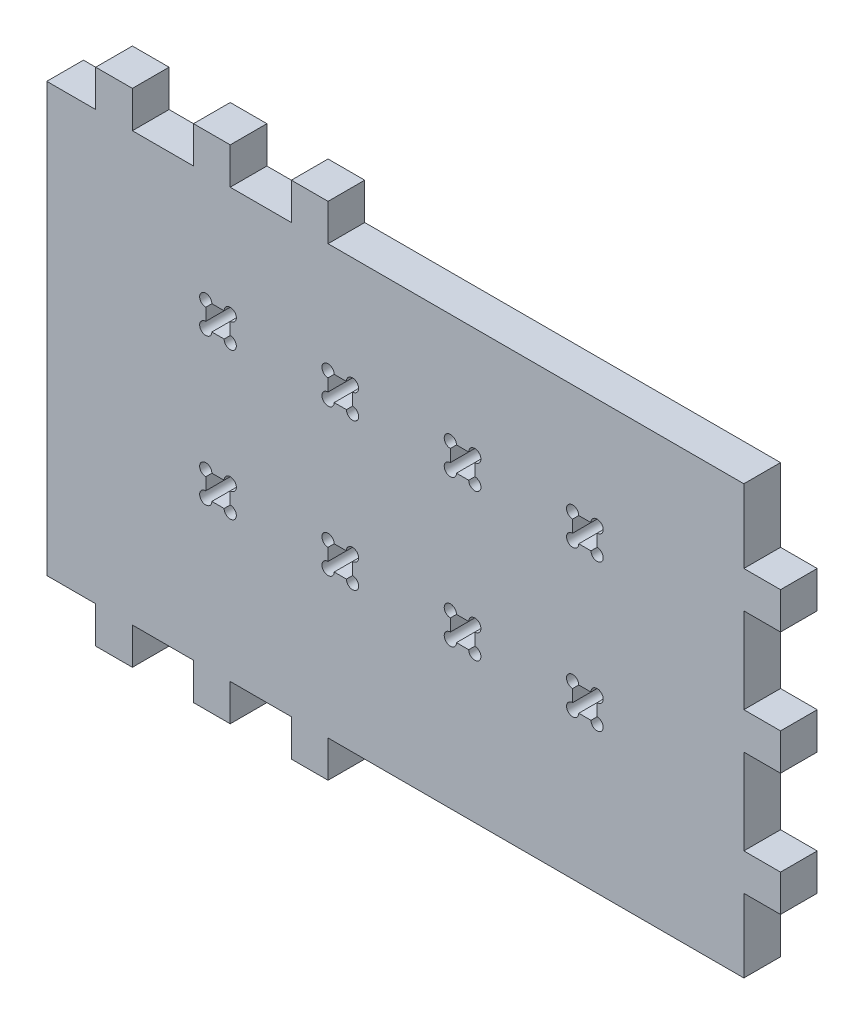
SolidWorks part; units mm, degrees
material "Balsa"
ref_plane "Front Plane" through (0, 0, 0) normal (0, 0, 1) x (1, 0, 0)
ref_plane "Top Plane" through (0, 0, 0) normal (0, 1, 0) x (1, 0, 0)
ref_plane "Right Plane" through (0, 0, 0) normal (1, 0, 0) x (0, 0, -1)
sketch "Sketch1" plane through (0, 0, 0) normal (0, 0, 1) x (1, 0, 0)
  line L1 (0, 0) -> (361.95, 0)
  line L2 (0, 0) -> (0, 222.25)
  line L3 (0, 222.25) -> (361.95, 222.25)
  line L4 (361.95, 0) -> (361.95, 222.25)
  dimension "D1" = 361.95
  dimension "D2" = 222.25
extrude "Boss-Extrude1" add sketch "Sketch1" against normal blind 19.05
sketch "Sketch2" plane through (0, 0, 0) normal (0, 0, 1) x (1, 0, 0)
  line L0 (0, 152.4) -> (361.95, 152.4)
  line L3 (0, 82.55) -> (361.95, 82.55)
  line L4 (0, 12.7) -> (361.95, 12.7) construction
  line L6 (0, 0) -> (361.95, 0) construction
  line L7 (0, 222.25) -> (0, 0) construction
  line L8 (361.95, 0) -> (361.95, 222.25) construction
  line L9 (0, 152.4) -> (-25.4, 152.4)
  line L10 (0, 82.55) -> (-25.4, 82.55)
  line L11 (0, 12.7) -> (-25.4, 12.7) construction
  line L12 (361.95, 12.7) -> (387.35, 12.7) construction
  line L13 (361.95, 82.55) -> (387.35, 82.55)
  line L14 (361.95, 152.4) -> (387.35, 152.4)
  dimension "D1" = 69.85
  dimension "D2" = 69.85
  dimension "D3" = 69.85
  dimension "5" = 0
  dimension "D4" = 25.4
  dimension "D5" = 12.7
sketch "Sketch3" plane through (0, 0, 0) normal (0, 0, 1) x (1, 0, 0)
  line L0 (44.45, 241.3) -> (76.2, 241.3) construction
  line L5 (95.25, 241.3) -> (127, 241.3) construction
  line L10 (361.95, 222.25) -> (0, 222.25) construction
  line L11 (25.4, 222.25) -> (44.45, 222.25)
  line L12 (25.4, 222.25) -> (25.4, 241.3)
  line L13 (25.4, 241.3) -> (44.45, 241.3)
  line L14 (44.45, 222.25) -> (44.45, 241.3)
  line L16 (0, 222.25) -> (0, 0) construction
  line L18 (76.2, 222.25) -> (95.25, 222.25)
  line L19 (76.2, 222.25) -> (76.2, 241.3)
  line L20 (76.2, 241.3) -> (95.25, 241.3)
  line L21 (95.25, 222.25) -> (95.25, 241.3)
  line L22 (146.05, 222.25) -> (127, 222.25)
  line L23 (146.05, 222.25) -> (146.05, 241.3)
  line L24 (146.05, 241.3) -> (127, 241.3)
  line L25 (127, 222.25) -> (127, 241.3)
  dimension "D1" = 19.05
  dimension "D2" = 25.4
  dimension "D3" = 127
extrude "Boss-Extrude4" add sketch "Sketch3" along direction (0, 0, -1) on the side against the normal up to surface (19.05 mm away) up to face at (180.975, 111.125, -19.05)
ref_plane "Plane1" through (0, 111.125, 0) normal (0, 1, 0) x (1, 0, 0)
mirror "Mirror1" about plane through (0, 111.125, 0) normal (0, 1, 0) of "Boss-Extrude4"
ref_plane "Plane2" through (0, 0, -9.525) normal (0, 0, 1) x (1, 0, 0)
sketch "Sketch5" plane through (0, 0, 0) normal (0, 0, 1) x (1, 0, 0)
  line L0 (361.95, 0) -> (361.95, 222.25) construction
  line L1 (361.95, 184.15) -> (381, 184.15)
  line L2 (361.95, 184.15) -> (361.95, 165.1)
  line L3 (361.95, 165.1) -> (381, 165.1)
  line L4 (381, 184.15) -> (381, 165.1)
  line L5 (361.95, 0) -> (361.95, 222.25) construction
  line L6 (361.95, 38.1) -> (381, 38.1)
  line L7 (361.95, 38.1) -> (361.95, 57.15)
  line L8 (361.95, 57.15) -> (381, 57.15)
  line L9 (381, 38.1) -> (381, 57.15)
  line L10 (361.95, 222.25) -> (361.95, 184.15) construction
  line L11 (361.95, 0) -> (361.95, 38.1) construction
  line L12 (361.95, 0) -> (361.95, 222.25) construction
  line L13 (361.95, 120.65) -> (381, 120.65)
  line L14 (361.95, 120.65) -> (361.95, 101.6)
  line L15 (361.95, 101.6) -> (381, 101.6)
  line L16 (381, 120.65) -> (381, 101.6)
  dimension "D1" = 19.05
  dimension "D2" = 38.1
  dimension "D3" = 44.45
  dimension "D4" = 38.1
extrude "Boss-Extrude5" add sketch "Sketch5" against normal up to surface (19.05 mm away) up to face at (99.3321, 111.125, -19.05)
sketch "Sketch6" plane through (0, 0, 0) normal (0, 0, 1) x (1, 0, 0)
  line L0 (0, 222.25) -> (0, 0) construction
  line L1 (85.725, 88.9) -> (92.075, 88.9)
  line L2 (82.55, 85.725) -> (82.55, 79.375)
  line L3 (85.725, 76.2) -> (92.075, 76.2)
  line L4 (95.25, 85.725) -> (95.25, 79.375)
  line L5 (0, 0) -> (25.4, 0) construction
  line L28 (149.225, 76.2) -> (155.575, 76.2)
  line L63 (158.75, 85.725) -> (158.75, 79.375)
  line L64 (149.225, 88.9) -> (155.575, 88.9)
  line L65 (44.45, -19.05) -> (25.4, -19.05) construction
  line L66 (146.05, 85.725) -> (146.05, 79.375)
  line L67 (212.725, 76.2) -> (219.075, 76.2)
  line L68 (222.25, 85.725) -> (222.25, 79.375)
  line L69 (212.725, 88.9) -> (219.075, 88.9)
  line L70 (209.55, 85.725) -> (209.55, 79.375)
  line L71 (276.225, 76.2) -> (282.575, 76.2)
  line L72 (285.75, 85.725) -> (285.75, 79.375)
  line L73 (276.225, 88.9) -> (282.575, 88.9)
  line L74 (273.05, 85.725) -> (273.05, 79.375)
  line L75 (149.225, 152.4) -> (155.575, 152.4)
  line L76 (158.75, 161.925) -> (158.75, 155.575)
  line L77 (149.225, 165.1) -> (155.575, 165.1)
  line L78 (146.05, 161.925) -> (146.05, 155.575)
  line L79 (212.725, 152.4) -> (219.075, 152.4)
  line L80 (222.25, 161.925) -> (222.25, 155.575)
  line L81 (212.725, 165.1) -> (219.075, 165.1)
  line L82 (209.55, 161.925) -> (209.55, 155.575)
  line L83 (276.225, 152.4) -> (282.575, 152.4)
  line L84 (285.75, 161.925) -> (285.75, 155.575)
  line L85 (276.225, 165.1) -> (282.575, 165.1)
  line L86 (273.05, 161.925) -> (273.05, 155.575)
  line L87 (85.725, 152.4) -> (92.075, 152.4)
  line L88 (95.25, 161.925) -> (95.25, 155.575)
  line L89 (85.725, 165.1) -> (92.075, 165.1)
  line L90 (82.55, 161.925) -> (82.55, 155.575)
  line L91 (82.55, 79.375) -> (146.05, 79.375) construction
  line L92 (82.55, 79.375) -> (82.55, 155.575) construction
  arc A20 (85.725, 88.9) -> (82.55, 85.725) centre (82.55, 88.9) ccw
  arc A21 (95.25, 85.725) -> (92.075, 88.9) centre (95.25, 88.9) ccw
  arc A22 (82.55, 79.375) -> (85.725, 76.2) centre (82.55, 76.2) ccw
  arc A23 (92.075, 76.2) -> (95.25, 79.375) centre (95.25, 76.2) ccw
  arc A24 (146.05, 79.375) -> (149.225, 76.2) centre (146.05, 76.2) ccw
  arc A25 (155.575, 76.2) -> (158.75, 79.375) centre (158.75, 76.2) ccw
  arc A26 (158.75, 85.725) -> (155.575, 88.9) centre (158.75, 88.9) ccw
  arc A27 (149.225, 88.9) -> (146.05, 85.725) centre (146.05, 88.9) ccw
  arc A28 (209.55, 79.375) -> (212.725, 76.2) centre (209.55, 76.2) ccw
  arc A29 (219.075, 76.2) -> (222.25, 79.375) centre (222.25, 76.2) ccw
  arc A30 (222.25, 85.725) -> (219.075, 88.9) centre (222.25, 88.9) ccw
  arc A31 (212.725, 88.9) -> (209.55, 85.725) centre (209.55, 88.9) ccw
  arc A32 (273.05, 79.375) -> (276.225, 76.2) centre (273.05, 76.2) ccw
  arc A33 (282.575, 76.2) -> (285.75, 79.375) centre (285.75, 76.2) ccw
  arc A34 (285.75, 85.725) -> (282.575, 88.9) centre (285.75, 88.9) ccw
  arc A35 (276.225, 88.9) -> (273.05, 85.725) centre (273.05, 88.9) ccw
  arc A36 (146.05, 155.575) -> (149.225, 152.4) centre (146.05, 152.4) ccw
  arc A37 (155.575, 152.4) -> (158.75, 155.575) centre (158.75, 152.4) ccw
  arc A38 (158.75, 161.925) -> (155.575, 165.1) centre (158.75, 165.1) ccw
  arc A39 (149.225, 165.1) -> (146.05, 161.925) centre (146.05, 165.1) ccw
  arc A40 (209.55, 155.575) -> (212.725, 152.4) centre (209.55, 152.4) ccw
  arc A41 (219.075, 152.4) -> (222.25, 155.575) centre (222.25, 152.4) ccw
  arc A42 (222.25, 161.925) -> (219.075, 165.1) centre (222.25, 165.1) ccw
  arc A43 (212.725, 165.1) -> (209.55, 161.925) centre (209.55, 165.1) ccw
  arc A44 (273.05, 155.575) -> (276.225, 152.4) centre (273.05, 152.4) ccw
  arc A45 (282.575, 152.4) -> (285.75, 155.575) centre (285.75, 152.4) ccw
  arc A46 (285.75, 161.925) -> (282.575, 165.1) centre (285.75, 165.1) ccw
  arc A47 (276.225, 165.1) -> (273.05, 161.925) centre (273.05, 165.1) ccw
  arc A48 (82.55, 155.575) -> (85.725, 152.4) centre (82.55, 152.4) ccw
  arc A49 (92.075, 152.4) -> (95.25, 155.575) centre (95.25, 152.4) ccw
  arc A50 (95.25, 161.925) -> (92.075, 165.1) centre (95.25, 165.1) ccw
  arc A51 (85.725, 165.1) -> (82.55, 161.925) centre (82.55, 165.1) ccw
  dimension "D10" = 76.2
  dimension "D5" = 6.35
  dimension "D1" = 82.55
  dimension "D2" = 12.7
  dimension "D3" = 12.7
  dimension "D4" = 76.2
  dimension "D6" = 4
  dimension "D8" = 90
  dimension "D9" = 63.5
  dimension "D7" = 2
extrude "Cut-Extrude2" cut sketch "Sketch6" against normal through all both
equation "\"ShelfSpacing\"=2.75"
equation "\"D1@Sketch2\"=\"ShelfSpacing\""
equation "\"D2@Sketch2\"=\"ShelfSpacing\""
equation "\"D3@Sketch2\"=\"ShelfSpacing\""
